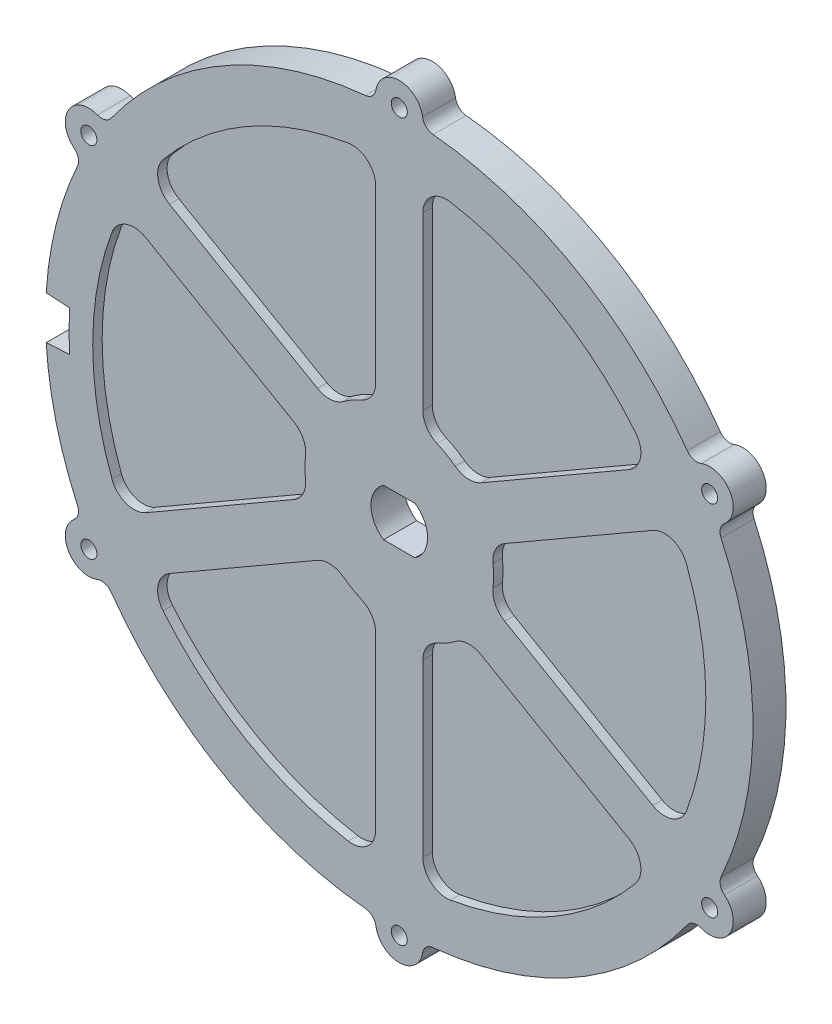
SolidWorks part; units mm, degrees
material "PETG"
ref_plane "Front Plane" through (0, 0, 0) normal (0, 0, 1) x (1, 0, 0)
ref_plane "Top Plane" through (0, 0, 0) normal (0, 1, 0) x (1, 0, 0)
ref_plane "Right Plane" through (0, 0, 0) normal (1, 0, 0) x (0, 0, -1)
sketch "Sketch2" plane through (0, 0, 0) normal (0, 0, 1) x (1, 0, 0)
  line L0 (3.3166, 5) -> (-3.3166, 5)
  line L1 (3.3166, -5) -> (-3.3166, -5)
  circle A0 centre (0, 0) radius 75
  circle A1 centre (0, 0) radius 6
  dimension "D1" = 150
  dimension "D2" = 12
  dimension "D3" = 10
extrude "Boss-Extrude1" add sketch "Sketch2" along normal mid plane 7 contours A0 A1 | L0 A1 | L1 A1 region at (0, 5.403, 0) region at (0, -5.403, 0) region at (-72.8787, 0, 0)
sketch "Sketch4" plane through (0, 0, -3.5) normal (0, 0, 1) x (1, 0, 0)
  line L0 (5, 76) -> (5, 74.8331)
  line L1 (-5, 76) -> (-5, 74.8331)
  arc A0 (5, 76) -> (-5, 76) centre (0, 76) ccw
  circle A1 centre (0, 0) radius 75 construction
  circle A3 centre (0, 0) radius 75
  arc A4 (-5, 74.8331) -> (5, 74.8331) centre (0, 0) ccw
  circle M9 centre (0, 0) radius 75
  dimension "D1" = 5
  dimension "D2" = 76
  dimension "D3" = 0
extrude "Boss-Extrude3" add sketch "Sketch4" along normal up to surface (7 mm away) contours A0 L0 L1 M9 region at (0, 77.5604, -3.5) up to face at (0, 0, 3.5)
fillet "Fillet1" radius 2.5 2 edges at (-5, 74.8331, 0) (5, 74.8331, 0)
sketch "Sketch6" plane through (0, 0, -3.5) normal (0, 0, -1) x (-1, 0, 0)
  circle A0 centre (0, 76) radius 1.7
  arc A4 (4.9414, 76.7632) -> (-4.9414, 76.7632) centre (0, 76) ccw construction
  dimension "D1" = 3.4
extrude "Cut-Extrude1" cut sketch "Sketch6" against normal through all
pattern_circular "CirPattern1" count 6 over 360 about axis through (0, 0, -3.5) along (0, 0, 1) of "Boss-Extrude3", "Cut-Extrude1", "Fillet1"
sketch "Sketch7" plane through (0, 0, -3.5) normal (0, 0, -1) x (-1, 0, 0)
  line L0 (-5, 59.1608) -> (-5, 22.9129)
  line L1 (5, 59.1608) -> (5, 22.9129)
  line L2 (-5, 19.3649) -> (5, 19.3649) construction
  line L3 (48.7348, 33.9105) -> (17.3431, 15.7866)
  line L4 (53.7348, 25.2503) -> (22.3431, 7.1263)
  line L6 (53.7348, -25.2503) -> (22.3431, -7.1263)
  line L7 (48.7348, -33.9105) -> (17.3431, -15.7866)
  line L9 (5, -59.1608) -> (5, -22.9129)
  line L10 (-5, -59.1608) -> (-5, -22.9129)
  line L12 (-48.7348, -33.9105) -> (-17.3431, -15.7866)
  line L13 (-53.7348, -25.2503) -> (-22.3431, -7.1263)
  line L15 (-53.7348, 25.2503) -> (-22.3431, 7.1263)
  line L16 (-48.7348, 33.9105) -> (-17.3431, 15.7866)
  line L18 (0, 0) -> (8, 18.3303) construction
  line L19 (14.2705, 14.0126) -> (19.2705, 5.3523) construction
  line L20 (19.2705, -5.3523) -> (14.2705, -14.0126) construction
  line L21 (5, -19.3649) -> (-5, -19.3649) construction
  line L22 (-14.2705, -14.0126) -> (-19.2705, -5.3523) construction
  line L23 (-19.2705, 5.3523) -> (-14.2705, 14.0126) construction
  arc A0 (-8, 18.3303) -> (-11.8745, 16.0934) centre (0, 0) ccw
  arc A1 (-10.8333, 64.0909) -> (-50.0876, 41.4274) centre (0, 0) ccw
  arc A2 (5, 22.9129) -> (8, 18.3303) centre (10, 22.9129) ccw
  arc A3 (5, 59.1608) -> (10.8333, 64.0909) centre (10, 59.1608) cw
  arc A4 (-5, 59.1608) -> (-10.8333, 64.0909) centre (-10, 59.1608) ccw
  arc A5 (-5, 22.9129) -> (-8, 18.3303) centre (-10, 22.9129) cw
  arc A6 (22.3431, 7.1263) -> (19.8745, 2.2369) centre (24.8431, 2.7962) ccw
  arc A7 (53.7348, 25.2503) -> (60.921, 22.6635) centre (56.2348, 20.9201) cw
  arc A8 (48.7348, 33.9105) -> (50.0876, 41.4274) centre (46.2348, 38.2407) ccw
  arc A9 (17.3431, 15.7866) -> (11.8745, 16.0934) centre (14.8431, 20.1167) cw
  arc A10 (17.3431, -15.7866) -> (11.8745, -16.0934) centre (14.8431, -20.1167) ccw
  arc A11 (48.7348, -33.9105) -> (50.0876, -41.4274) centre (46.2348, -38.2407) cw
  arc A12 (53.7348, -25.2503) -> (60.921, -22.6635) centre (56.2348, -20.9201) ccw
  arc A13 (22.3431, -7.1263) -> (19.8745, -2.2369) centre (24.8431, -2.7962) cw
  arc A14 (-5, -22.9129) -> (-8, -18.3303) centre (-10, -22.9129) ccw
  arc A15 (-5, -59.1608) -> (-10.8333, -64.0909) centre (-10, -59.1608) cw
  arc A16 (5, -59.1608) -> (10.8333, -64.0909) centre (10, -59.1608) ccw
  arc A17 (5, -22.9129) -> (8, -18.3303) centre (10, -22.9129) cw
  arc A18 (-22.3431, -7.1263) -> (-19.8745, -2.2369) centre (-24.8431, -2.7962) ccw
  arc A19 (-53.7348, -25.2503) -> (-60.921, -22.6635) centre (-56.2348, -20.9201) cw
  arc A20 (-48.7348, -33.9105) -> (-50.0876, -41.4274) centre (-46.2348, -38.2407) ccw
  arc A21 (-17.3431, -15.7866) -> (-11.8745, -16.0934) centre (-14.8431, -20.1167) cw
  arc A22 (-17.3431, 15.7866) -> (-11.8745, 16.0934) centre (-14.8431, 20.1167) ccw
  arc A23 (-48.7348, 33.9105) -> (-50.0876, 41.4274) centre (-46.2348, 38.2407) cw
  arc A24 (-53.7348, 25.2503) -> (-60.921, 22.6635) centre (-56.2348, 20.9201) ccw
  arc A25 (-22.3431, 7.1263) -> (-19.8745, 2.2369) centre (-24.8431, 2.7962) cw
  arc A26 (11.8745, 16.0934) -> (8, 18.3303) centre (0, 0) ccw
  arc A27 (19.8745, -2.2369) -> (19.8745, 2.2369) centre (0, 0) ccw
  arc A28 (8, -18.3303) -> (11.8745, -16.0934) centre (0, 0) ccw
  arc A29 (-11.8745, -16.0934) -> (-8, -18.3303) centre (0, 0) ccw
  arc A30 (-19.8745, 2.2369) -> (-19.8745, -2.2369) centre (0, 0) ccw
  arc A31 (50.0876, 41.4274) -> (10.8333, 64.0909) centre (0, 0) ccw
  arc A32 (60.921, -22.6635) -> (60.921, 22.6635) centre (0, 0) ccw
  arc A33 (10.8333, -64.0909) -> (50.0876, -41.4274) centre (0, 0) ccw
  arc A34 (-50.0876, -41.4274) -> (-10.8333, -64.0909) centre (0, 0) ccw
  arc A35 (-60.921, 22.6635) -> (-60.921, -22.6635) centre (0, 0) ccw
  point P8 (0, 19.3649)
  dimension "D1" = 130
  dimension "D2" = 40
  dimension "D4" = 5
  dimension "D3" = 10
  dimension "D5" = 6
extrude "Cut-Extrude2" cut sketch "Sketch7" against normal blind 2
mirror "Mirror1" about plane through (0, 0, 0) normal (0, 0, 1) of "Cut-Extrude2"
sketch "Sketch9" plane through (0, 0, 0) normal (0, 1, 0) x (1, 0, 0)
  line L0 (-7.173, 3.5) -> (-61.0677, 3.5) construction
  line L1 (-75, -3.5) -> (-70, -3.5)
  line L2 (-75, -3.5) -> (-75, 3.5)
  line L3 (-75, 3.5) -> (-70, 3.5)
  line L4 (-70, -3.5) -> (-70, 3.5)
  line L5 (-61.0677, -3.5) -> (-7.173, -3.5) construction
  line L6 (0, 0) -> (0, 49.8627) construction
  line L7 (-68.2407, 3.5) -> (-75, 3.5) construction
  line L8 (-75, 3.5) -> (-75, -3.5) construction
  dimension "D1" = 5
revolve "Cut-Revolve1" cut sketch "Sketch9" angle 7 mid plane about L6
